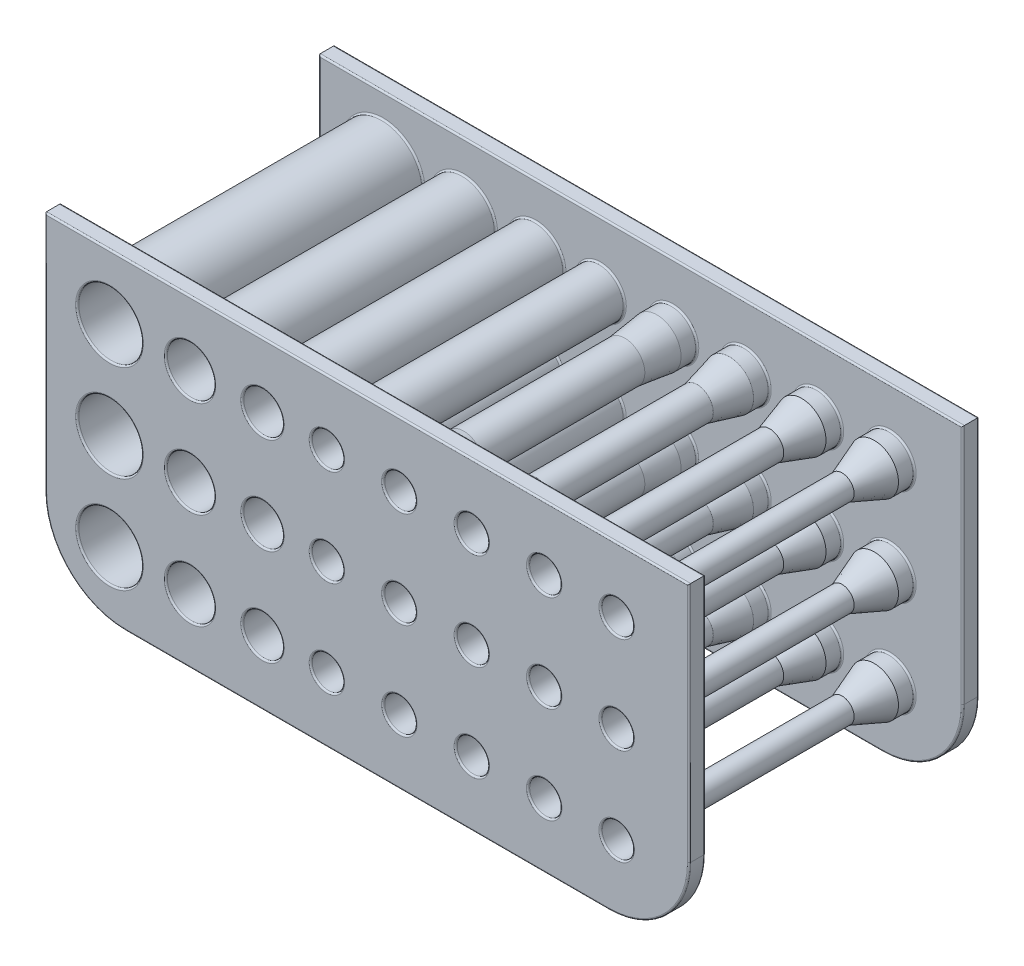
SolidWorks part; units mm, degrees
ref_plane "Ebene vorne" through (0, 0, 0) normal (0, 0, 1) x (1, 0, 0)
ref_plane "Ebene oben" through (0, 0, 0) normal (0, 1, 0) x (1, 0, 0)
ref_plane "Ebene rechts" through (0, 0, 0) normal (1, 0, 0) x (0, 0, -1)
sketch "Skizze1" plane through (0, 0, 0) normal (0, 0, 1) x (1, 0, 0)
  line L0 (-40, 0) -> (40, 0) construction
  line L1 (-40, -16) -> (40, -16) construction
  line L2 (-40, -16) -> (-40, 16) construction
  line L3 (-40, 16) -> (40, 16) construction
  line L4 (40, -16) -> (40, 16) construction
  line L5 (-40, -16) -> (40, 16) construction
  line L6 (-40, 16) -> (40, -16) construction
  circle A12 centre (-32, 0) radius 4
  circle A14 centre (-22, 0) radius 3
  circle A22 centre (-13, 0) radius 2.5
  circle A26 centre (-5, 0) radius 2
  circle A32 centre (4, 0) radius 1.5
  circle A40 centre (13, 0) radius 1
  circle A48 centre (22, 0) radius 0.75
  circle A54 centre (31, 0) radius 0.5
  point P0 (0, 0)
  dimension "D7" = 8
  dimension "D9" = 6
  dimension "D17" = 5
  dimension "D21" = 4
  dimension "D27" = 3
  dimension "D35" = 2
  dimension "D43" = 1.5
  dimension "D49" = 1
  dimension "D1" = 32
  dimension "D2" = 80
extrude "Extrude-Thin2" add sketch "Skizze1" along normal mid plane 36 thin thin type one direction wall 1
ref_plane "Plane1" through (0, 0, 18) normal (0, 0, 1) x (1, 0, 0)
ref_plane "Plane2" through (0, 0, -18) normal (0, 0, 1) x (1, 0, 0)
sketch "Sketch1" plane through (0, 0, 18) normal (0, 0, 1) x (1, 0, 0)
  line L1 (-40, 20) -> (40, 20)
  line L2 (-40, 20) -> (-40, -20)
  line L3 (-40, -20) -> (40, -20)
  line L4 (40, 20) -> (40, -20)
  line L5 (-40, 20) -> (40, -20) construction
  line L6 (-40, -20) -> (40, 20) construction
  point P0 (0, 0)
  point P21 (0, 0)
  dimension "D1" = 80
  dimension "D2" = 40
extrude "Boss-Extrude1" add sketch "Sketch1" against normal blind 2
sketch "Sketch7" plane through (0, 0, 18) normal (0, 0, 1) x (1, 0, 0)
  circle A0 centre (31, 0) radius 3
  circle A1 centre (22, 0) radius 3
  circle A2 centre (13, 0) radius 3
  circle A3 centre (4, 0) radius 3
fillet "Fillet1" radius 10 2 edges at (40, -20, 17) (-40, -20, 17)
pattern_linear "LPattern2" count 2 spacing 34 along (0, 0, -1) of "Boss-Extrude1", "Fillet1"
extrude "Cut-Extrude1" cut sketch "Skizze1<3>" against normal mid plane 36
sketch "Skizze1<3>" plane through (0, 0, 0) normal (0, 0, 1) x (1, 0, 0) same geometry as "Skizze1"
extrude "Cut-Extrude2" cut sketch "Sketch7" against normal blind 8
extrude "Extrude-Thin3" add sketch "Sketch7<3>" against normal blind 4 thin thin type one direction reverse wall 1
sketch "Sketch7<3>" plane through (0, 0, 18) normal (0, 0, 1) x (1, 0, 0) same geometry as "Sketch7"
sketch "Sketch22" plane through (0, 0, 0) normal (0, 1, 0) x (1, 0, 0)
  line L0 (15, -10) -> (16, -14)
  line L1 (16, -14) -> (15, -14)
  line L2 (15, -14) -> (14, -10)
  line L3 (15, -10) -> (14, -10)
sketch "Sketch23" plane through (0, 0, 0) normal (0, 1, 0) x (1, 0, 0)
  line L0 (23.75, -10) -> (25, -14)
  line L1 (25, -14) -> (24, -14)
  line L2 (24, -14) -> (22.75, -10)
  line L3 (22.75, -10) -> (23.75, -10)
sketch "Sketch24" plane through (0, 0, 0) normal (0, 1, 0) x (1, 0, 0)
  line L0 (34, -14) -> (33, -14)
  line L1 (33, -14) -> (31.5, -10)
  line L2 (31.5, -10) -> (32.5, -10)
  line L3 (32.5, -10) -> (34, -14)
ref_axis "Axis2" through (4, 0, 14) along (0, 0, 1)
ref_axis "Axis3" through (22, 0, 14) along (0, 0, 1)
ref_axis "Axis4" through (13, 0, 14) along (0, 0, 1)
ref_axis "Axis5" through (31, 0, 14) along (0, 0, 1)
sketch "Sketch8" plane through (0, 0, 0) normal (0, 1, 0) x (1, 0, 0)
  line L0 (6, -14) -> (7, -14)
  line L1 (7, -14) -> (6.5, -10)
  line L2 (6.5, -10) -> (5.5, -10)
  line L3 (5.5, -10) -> (6, -14)
revolve "Revolve2" add sketch "Sketch8" angle 360 about axis through (4, 0, 14) along (0, 0, 1)
revolve "Revolve3" add sketch "Sketch22" angle 360 about axis through (13, 0, 14) along (0, 0, 1)
revolve "Revolve4" add sketch "Sketch23" angle 360 about axis through (22, 0, 14) along (0, 0, 1)
revolve "Revolve5" add sketch "Sketch24" angle 360 about axis through (31, 0, 14) along (0, 0, 1)
mirror "Mirror6" about plane through (0, 0, 0) normal (0, 0, 1) of "Cut-Extrude2", "Extrude-Thin3", "Revolve3", "Revolve4", "Revolve5", "Revolve2"
pattern_linear "LPattern5" count 2 spacing 12 along (0, -1, 0) count 2 spacing 12 along (0, 1, 0) of "Cut-Extrude1", "Revolve5", "Revolve4", "Revolve3", "Revolve2", "Extrude-Thin3", "Cut-Extrude2", "Extrude-Thin2", "Mirror6"
fillet "Fillet3" radius 0.2 120 edges at (6, 0, -18) (15, 0, -18) (24, 0, -18) (33, 0, -18) (6, -12, -18) (15, -12, -18) (24, -12, -18) (33, -12, -18) (6, 12, -18) (15, 12, -18) (24, 12, -18) (33, 12, -18) (-10.5, 0, -18) (-28, 0, -18) (0, 20, -18) (-40, 5, -18) (-37.0711, -17.0711, -18) (0, -20, -18) (37.0711, -17.0711, -18) (40, 5, -18) (-19, 0, -18) (-3, 0, -18) (-28, 12, -18) (-28, -12, -18) (-3, 12, -18) (-10.5, 12, -18) (-19, 12, -18) (-3, -12, -18) (-10.5, -12, -18) (-19, -12, -18) (-37.0711, -17.0711, -16) (-40, 5, -16) (0, 20, -16) (40, 5, -16) (37.0711, -17.0711, -16) (0, -20, -16) (-2, 0, -16) (-9.5, 0, -16) (-18, 0, -16) (-27, 0, -16) (7, 0, -16) (16, 0, -16) (25, 0, -16) (34, 0, -16) (-27, 12, -16) (-18, 12, -16) (-9.5, 12, -16) (-2, 12, -16) (-27, -12, -16) (-18, -12, -16) (-9.5, -12, -16) (-2, -12, -16) (7, 12, -16) (16, 12, -16) (25, 12, -16) (34, 12, -16) (7, -12, -16) (16, -12, -16) (25, -12, -16) (34, -12, -16) (6, 0, 18) (15, 0, 18) (24, 0, 18) (33, 0, 18) (6, -12, 18) (15, -12, 18) (24, -12, 18) (33, -12, 18) (6, 12, 18) (15, 12, 18) (24, 12, 18) (33, 12, 18) (-10.5, 0, 18) (-28, 0, 18) (-37.0711, -17.0711, 18) (-40, 5, 18) (0, 20, 18) (40, 5, 18) (37.0711, -17.0711, 18) (0, -20, 18) (-19, 0, 18) (-3, 0, 18) (-28, 12, 18) (-28, -12, 18) (-3, 12, 18) (-10.5, 12, 18) (-19, 12, 18) (-3, -12, 18) (-10.5, -12, 18) (-19, -12, 18) (0, 20, 16) (-40, 5, 16) (-37.0711, -17.0711, 16) (0, -20, 16) (37.0711, -17.0711, 16) (40, 5, 16) (-27, 0, 16) (-18, 0, 16) (-9.5, 0, 16) (-2, 0, 16) (7, 0, 16) (16, 0, 16) (25, 0, 16) (34, 0, 16) (-27, 12, 16) (-18, 12, 16) (-9.5, 12, 16) (-2, 12, 16) (-27, -12, 16) (-18, -12, 16) (-9.5, -12, 16) (-2, -12, 16) (34, 12, 16) (34, -12, 16) (7, 12, 16) (16, 12, 16) (25, 12, 16) (7, -12, 16) (16, -12, 16) (25, -12, 16)
